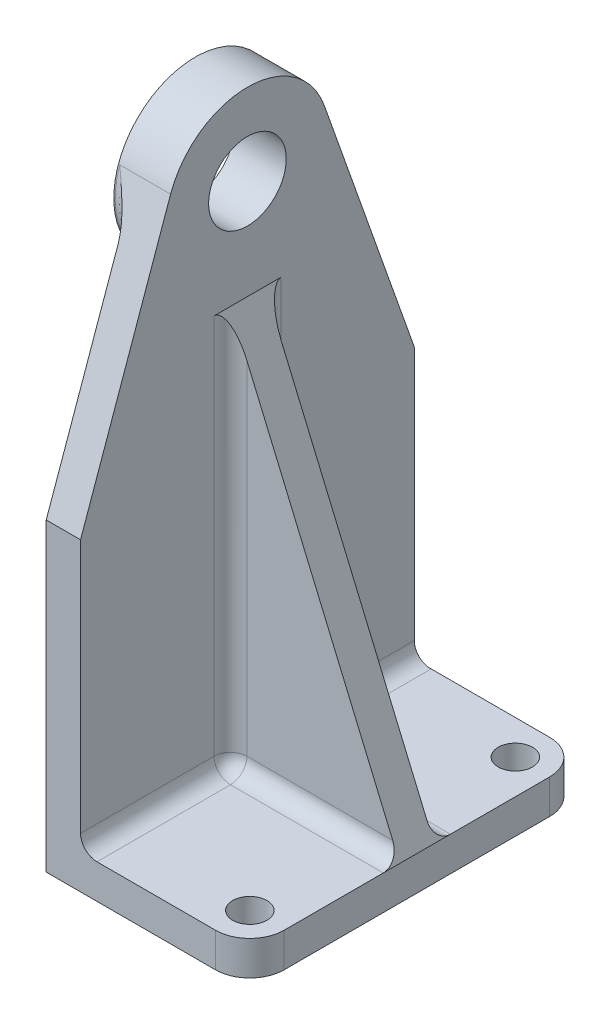
SolidWorks part; units mm, degrees
ref_plane "Front Plane" through (0, 0, 0) normal (0, 0, 1) x (1, 0, 0)
ref_plane "Top Plane" through (0, 0, 0) normal (0, 1, 0) x (1, 0, 0)
ref_plane "Right Plane" through (0, 0, 0) normal (1, 0, 0) x (0, 0, -1)
sketch "Sketch1" plane through (0, 0, 0) normal (1, 0, 0) x (0, 0, -1)
  line L0 (0, 33.2358) -> (0, 5.0201)
  line L2 (30.8829, 5.0201) -> (30.8829, 33.2358)
  line L4 (30.8829, 33.2358) -> (22.5499, 56.759)
  line L5 (0, 33.2358) -> (8.333, 56.759)
  line L6 (0, 5.0201) -> (30.8829, 5.0201)
  arc A0 (22.5499, 56.759) -> (8.333, 56.759) centre (15.4414, 54.2409) ccw
extrude "Extrude1" add sketch "Sketch1" against normal blind 3.175
ref_plane "Plane1" through (0, 5.0201, 0) normal (0, -1, 0) x (1, 0, 0)
sketch "Sketch2" plane through (0, 5.0201, 0) normal (0, -1, 0) x (1, 0, 0)
  line L0 (-3.175, 0) -> (-3.175, -30.8829) construction
  line L1 (-3.175, 0) -> (12.4866, 0)
  line L2 (-3.175, 0) -> (-3.175, -30.9163)
  line L3 (-3.175, -30.9163) -> (12.4866, -30.9163)
  line L4 (15.6616, -3.175) -> (15.6616, -27.7413)
  arc A0 (15.6616, -3.175) -> (12.4866, 0) centre (12.4866, -3.175) ccw
  arc A1 (12.4866, -30.9163) -> (15.6616, -27.7413) centre (12.4866, -27.7413) ccw
  circle A2 centre (12.4866, -3.175) radius 1.5875
  circle A3 centre (12.4866, -27.7413) radius 1.5875
  dimension "D1" = 3.175
  dimension "D2" = 3.175
  dimension "D3" = 3.175
extrude "Extrude2" add sketch "Sketch2" against normal blind 3.175
ref_plane "Plane2" through (0, 0, -15.4582) normal (0, 0, 1) x (1, 0, 0)
sketch "Sketch3" plane through (0, 0, -15.4582) normal (0, 0, 1) x (1, 0, 0)
  line L0 (15.6616, 8.1951) -> (0, 44.9974)
  line L1 (0, 56.759) -> (0, 33.2358) construction
  line L2 (0, 44.9974) -> (0, 8.1951)
  line L3 (0, 8.1951) -> (15.6616, 8.1951)
extrude "Extrude3" add sketch "Sketch3" along normal mid plane 3.175
ref_plane "Plane3" through (-3.175, 0, 0) normal (1, 0, 0) x (0, 0, -1)
sketch "Sketch4" plane through (-3.175, 0, 0) normal (1, 0, 0) x (0, 0, -1)
  circle A0 centre (15.4414, 54.2409) radius 7.5413
extrude "Extrude4" add sketch "Sketch4" against normal blind 1.651
fillet "Fillet2" radius 1.524 1 edges
fillet "Fillet3" radius 1.524 6 edges at (7.8308, 8.1951, -17.0457) (0, 8.1951, -23.9643) (0, 26.5963, -17.0457) (7.8308, 8.1951, -13.8707) (0, 8.1951, -6.9353) (0, 26.5963, -13.8707)
ref_plane "Plane4" through (-4.699, 0, 0) normal (1, 0, 0) x (0, 0, -1)
sketch "Sketch5" plane through (-4.699, 0, 0) normal (1, 0, 0) x (0, 0, -1)
  circle A0 centre (15.4414, 54.2409) radius 3.5894
extrude "Extrude5" cut sketch "Sketch5" along normal mid plane 16.383
